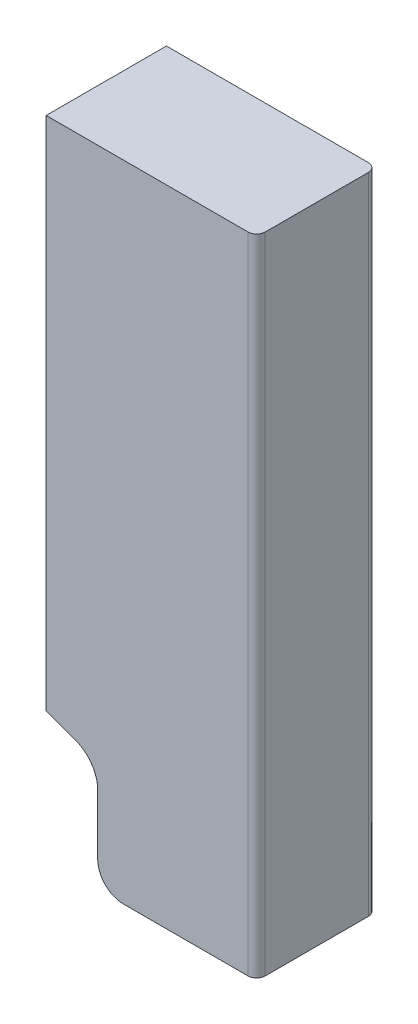
SolidWorks part; units mm, degrees
material "K110"
ref_plane "Front Plane" through (0, 0, 0) normal (0, 0, 1) x (1, 0, 0)
ref_plane "Top Plane" through (0, 0, 0) normal (0, 1, 0) x (1, 0, 0)
ref_plane "Right Plane" through (0, 0, 0) normal (1, 0, 0) x (0, 0, -1)
sketch "Sketch1" plane through (0, 0, 0) normal (0, 1, 0) x (1, 0, 0)
  line L1 (-12.25, -7) -> (12.25, -7)
  line L2 (-12.25, -7) -> (-12.25, 7)
  line L3 (-12.25, 7) -> (12.25, 7)
  line L4 (12.25, -7) -> (12.25, 7)
  line L5 (-12.25, -7) -> (12.25, 7) construction
  line L6 (-12.25, 7) -> (12.25, -7) construction
  point P0 (0, 0)
  dimension "D1" = 24.5
  dimension "D2" = 14
extrude "Boss-Extrude1" add sketch "Sketch1" against normal blind 75
sketch "Sketch2" plane through (0, 0, 7) normal (0, 0, 1) x (1, 0, 0)
  line L0 (-12.25, 0) -> (12.25, 0) construction
  line L1 (-12.25, -75) -> (-6.25, -75) construction
  line L2 (-12.25, -75) -> (-12.25, -61) construction
  line L3 (-12.25, -61) -> (-10.25, -61) construction
  line L4 (-6.25, -75) -> (-6.25, -65) construction
  line L5 (12.25, -75) -> (12.25, 0) construction
  line L6 (-8.8819, -61.2412) -> (-12.25, -60.0153)
  line L7 (-12.25, -75) -> (-12.25, 0) construction
  line L8 (-6.25, -65) -> (-6.25, -75)
  line L9 (-6.25, -75) -> (-12.25, -75)
  line L10 (-12.25, -75) -> (-12.25, -60.0153)
  arc A0 (-10.25, -61) -> (-6.25, -65) centre (-10.25, -65) cw construction
  arc A1 (-6.25, -65) -> (-8.8819, -61.2412) centre (-10.25, -65) ccw
  dimension "D3" = 4
  dimension "D1" = 61
  dimension "D2" = 18.5
  dimension "D4" = 2
  dimension "D5" = 20
extrude "Cut-Extrude1" cut sketch "Sketch2" against normal up to next
fillet "Fillet1" radius 3 1 edges at (-6.25, -75, 0)
fillet "Fillet2" radius 1 2 edges at (12.25, -37.5, -7) (12.25, -37.5, 7)
